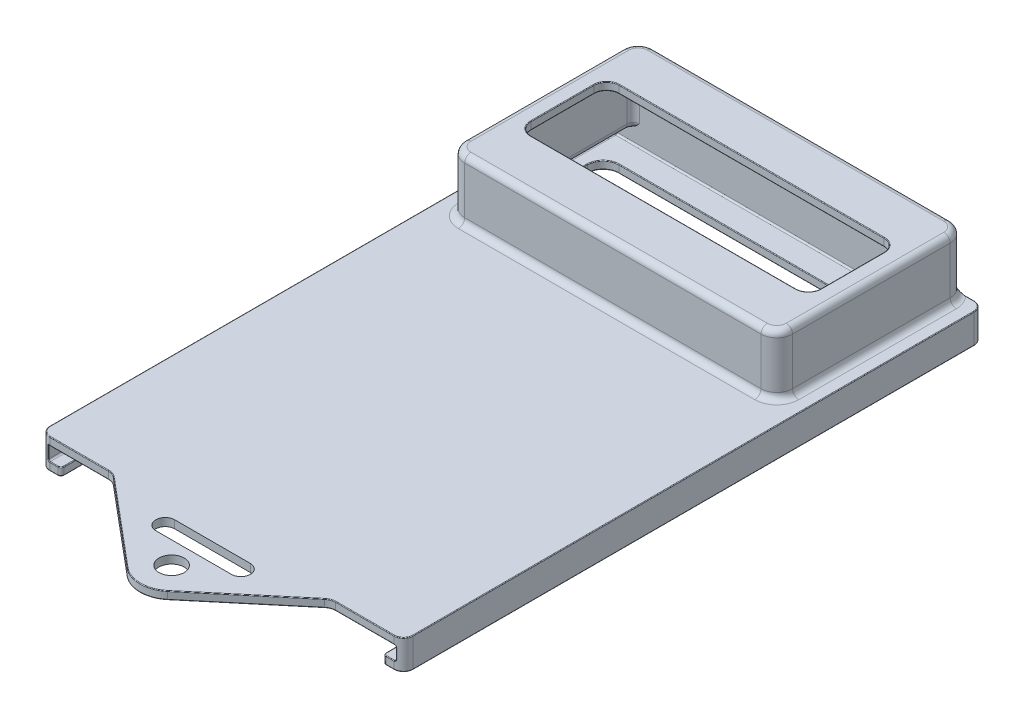
SolidWorks part; units mm, degrees
ref_plane "Спереди" through (0, 0, 0) normal (0, 0, 1) x (1, 0, 0)
ref_plane "Сверху" through (0, 0, 0) normal (0, 1, 0) x (1, 0, 0)
ref_plane "Справа" through (0, 0, 0) normal (1, 0, 0) x (0, 0, -1)
sketch "Эскиз1" plane through (0, 0, 0) normal (0, 0, 1) x (1, 0, 0)
  line L0 (-34.2552, 0) -> (0, 0) construction
  line L1 (0, 0) -> (0, 57.6) construction
  line L2 (27.55, 0) -> (-27.55, 0)
  line L3 (-27.55, 0) -> (-27.55, -2.2)
  line L4 (-27.55, -2.2) -> (-25.55, -2.2)
  line L5 (-25.55, -2.2) -> (-25.55, -3.45)
  line L6 (-25.55, -3.45) -> (-28.8, -3.45)
  line L7 (-28.8, -3.45) -> (-28.8, 1.25)
  line L8 (-28.8, 1.25) -> (28.8, 1.25)
  line L9 (28.8, -3.45) -> (28.8, 1.25)
  line L10 (25.55, -3.45) -> (28.8, -3.45)
  line L11 (25.55, -2.2) -> (25.55, -3.45)
  line L12 (27.55, -2.2) -> (25.55, -2.2)
  line L13 (27.55, 0) -> (27.55, -2.2)
  point P12 (0, 1.25)
  dimension "D1" = 55.1
  dimension "D2" = 2.2
  dimension "D3" = 1.25
  dimension "D4" = 1.25
  dimension "D5" = 57.6
  dimension "D6" = 51.1
  dimension "D7" = 1.25
extrude "Бобышка-Вытянуть1" add sketch "Эскиз1" against normal blind 92
sketch "Эскиз2" plane through (0, 0, -92) normal (0, 0, -1) x (-1, 0, 0)
  line L1 (-28.8, 1.25) -> (28.8, 1.25)
  line L2 (-28.8, 1.25) -> (-28.8, -3.45)
  line L3 (-28.8, -3.45) -> (28.8, -3.45)
  line L4 (28.8, 1.25) -> (28.8, -3.45)
extrude "Бобышка-Вытянуть2" add sketch "Эскиз2" against normal blind 2
sketch "Эскиз3" plane through (0, 1.25, 0) normal (0, 1, 0) x (1, 0, 0)
  line L0 (0, 0) -> (0, 92) construction
  line L1 (28.8, 92) -> (25.9495, 92) construction
  line L2 (-6, 2) -> (6, 2) construction
  line L3 (-6, 3) -> (6, 3)
  line L4 (-6, 1) -> (6, 1)
  line L5 (28.8, 0) -> (-28.8, 0) construction
  arc A0 (-6, 3) -> (-6, 1) centre (-6, 2) ccw
  arc A1 (6, 1) -> (6, 3) centre (6, 2) ccw
  point P7 (0, 2)
  dimension "D1" = 2
  dimension "D2" = 1
  dimension "D3" = 12
sketch "Эскиз4" plane through (0, 1.25, 0) normal (0, 1, 0) x (1, 0, 0)
  line L0 (0, 0) -> (0, 92) construction
  line L1 (28.8, 92) -> (25.9495, 92) construction
  line L3 (-26, 62) -> (26, 62)
  line L4 (-26, 62) -> (-26, 92)
  line L5 (-26, 92) -> (26, 92)
  line L6 (26, 62) -> (26, 92)
  line L7 (-26, 62) -> (26, 92) construction
  line L8 (-26, 92) -> (26, 62) construction
  point P5 (0, 77)
  dimension "D1" = 30
  dimension "D2" = 52
extrude "Бобышка-Вытянуть3" add sketch "Эскиз4" along normal blind 9.5
fillet "Скругление1" radius 2.5 4 edges at (26, 6, -92) (-26, 6, -92) (26, 6, -62) (-26, 6, -62)
fillet "Скругление2" radius 1 15 edges at (-25.2678, 1.25, -62.7322) (-26, 1.25, -77) (-25.2678, 1.25, -91.2678) (25.2678, 1.25, -91.2678) (26, 1.25, -77) (25.2678, 1.25, -62.7322) (25.2678, 10.75, -62.7322) (0, 10.75, -62) (-25.2678, 10.75, -62.7322) (-26, 10.75, -77) (-25.2678, 10.75, -91.2678) (0, 10.75, -92) (25.2678, 10.75, -91.2678) (26, 10.75, -77) (0, 1.25, -62)
sketch "Эскиз5" plane through (0, 0, 0) normal (0, -1, 0) x (1, 0, 0)
  line L9 (-26, -89.5) -> (-26, -64.5) construction
  line L10 (25.55, -90) -> (-25.55, -90) construction
  line L32 (-24.75, -64.5) -> (-24.75, -89)
  line L33 (-23.75, -90) -> (23.75, -90)
  line L34 (24.75, -89) -> (24.75, -64.5)
  line L35 (23.75, -63.5) -> (-23.75, -63.5)
  arc A24 (-23.75, -63.5) -> (-24.75, -64.5) centre (-23.75, -64.5) ccw
  arc A25 (-24.75, -89) -> (-23.75, -90) centre (-23.75, -89) ccw
  arc A26 (23.75, -90) -> (24.75, -89) centre (23.75, -89) ccw
  arc A27 (24.75, -64.5) -> (23.75, -63.5) centre (23.75, -64.5) ccw
  dimension "D4" = 1
  dimension "D1" = 26.5
  dimension "D2" = 1.25
  dimension "D3" = 49.5
extrude "Вырез-Вытянуть2" cut sketch "Эскиз5" against normal offset from surface (9.5 mm away) 1.25 up to face at (0, 10.75, -77)
fillet "Скругление3" radius 1 8 edges at (-24.4571, 9.5, -89.7071) (0, 9.5, -90) (24.4571, 9.5, -89.7071) (24.75, 9.5, -76.75) (24.4571, 9.5, -63.7929) (0, 9.5, -63.5) (-24.4571, 9.5, -63.7929) (-24.75, 9.5, -76.75)
fillet "Скругление4" radius 1 7 edges at (24.4571, 0, -89.7071) (-24.4571, 0, -89.7071) (-24.75, 0, -76.75) (-24.4571, 0, -63.7929) (0, 0, -63.5) (24.4571, 0, -63.7929) (24.75, 0, -76.75)
sketch "Эскиз7" plane through (0, 9.5, 0) normal (0, -1, 0) x (1, 0, 0)
  line L0 (0, 0) -> (0, -92) construction
  line L1 (-28.8, -92) -> (28.8, -92) construction
  line L2 (0, -101.75) -> (0, -77) construction
  line L3 (16, -84) -> (21, -84)
  line L4 (23, -82) -> (23, -72)
  line L5 (16, -70) -> (21, -70)
  line L6 (16, -84) -> (-16, -84)
  line L7 (16, -70) -> (-16, -70)
  line L8 (16, -77) -> (-16, -77) construction
  line L9 (16, -84) -> (-16, -84) construction
  line L10 (16, -70) -> (-16, -70) construction
  line L11 (0, -70) -> (0, -84) construction
  line L12 (-16, -84) -> (-21, -84)
  line L13 (-23, -82) -> (-23, -72)
  line L14 (-16, -70) -> (-21, -70)
  line L15 (0, -1.4349) -> (0, -77) construction
  line L16 (-16, -63) -> (-16, -70) construction
  line L17 (-23.5, -63) -> (23.5, -63) construction
  line L18 (-16, -84) -> (-16, -91) construction
  line L19 (23.5, -91) -> (-23.5, -91) construction
  arc A0 (21, -84) -> (23, -82) centre (21, -82) ccw
  arc A1 (21, -70) -> (23, -72) centre (21, -72) cw
  arc A2 (16, -84) -> (16, -70) centre (16, -77) ccw construction
  arc A3 (-16, -70) -> (-16, -84) centre (-16, -77) ccw construction
  arc A4 (-21, -84) -> (-23, -82) centre (-21, -82) cw
  arc A5 (-21, -70) -> (-23, -72) centre (-21, -72) ccw
  point P9 (0, -77)
  point P20 (23, -77)
  dimension "D3" = 46
  dimension "D1" = 2
  dimension "D4" = 2
  dimension "D2" = 14
  dimension "D5" = 15
  dimension "D6" = 23
extrude "Вырез-Вытянуть3" cut sketch "Эскиз7" against normal up to next
sketch "Эскиз8" plane through (0, -3.45, 0) normal (0, -1, 0) x (1, 0, 0)
  line L0 (-25.55, -90) -> (-25.55, 0) construction
  line L1 (-25.55, -86) -> (25.55, -86)
  line L2 (-25.55, -86) -> (-25.55, -90)
  line L3 (-25.55, -90) -> (25.55, -90)
  line L4 (25.55, -86) -> (25.55, -90)
  dimension "D1" = 4
extrude "Бобышка-Вытянуть4" add sketch "Эскиз8" against normal up to surface (1.25 mm away) up to face at (-26.55, -2.2, -45)
fillet "Скругление5" radius 1.5 4 edges at (-28.8, -1.1, 0) (28.8, -1.1, 0) (28.8, -1.1, -92) (-28.8, -1.1, -92)
fillet "Скругление6" radius 0.25 2 edges at (27.55, -1.1, -90) (-27.55, -1.1, -90)
sketch "Эскиз10" plane through (0, 0, 0) normal (0, -1, 0) x (1, 0, 0)
  line L0 (0, 0) -> (0, 13.6675) construction
  line L1 (6, 3) -> (-6, 3) construction
  line L2 (6, 1.5) -> (-6, 1.5)
  line L3 (6, 4.5) -> (-6, 4.5)
  line L4 (-27.3, 0) -> (27.3, 0) construction
  line L5 (-3.2139, 11.8302) -> (-17.3126, 0)
  line L6 (3.2139, 11.8302) -> (17.3126, 0)
  line L7 (-17.3126, 0) -> (-17.3126, -0.5)
  line L8 (-17.3126, -0.5) -> (17.3126, -0.5)
  line L9 (17.3126, -0.5) -> (17.3126, 0)
  circle A0 centre (0, 8) radius 2
  arc A1 (6, 1.5) -> (6, 4.5) centre (6, 3) ccw
  arc A2 (-6, 4.5) -> (-6, 1.5) centre (-6, 3) ccw
  arc A3 (3.2139, 11.8302) -> (-3.2139, 11.8302) centre (0, 8) ccw
  point P7 (0, 3)
  dimension "D1" = 4
  dimension "D6" = 10
  dimension "D2" = 3
  dimension "D3" = 12
  dimension "D4" = 3
  dimension "D5" = 5
  dimension "D7" = 40
  dimension "D8" = 0.5
extrude "Бобышка-Вытянуть6" add sketch "Эскиз10" against normal up to surface (1.25 mm away) up to face at (0, 1.25, -61.2976)
fillet "Скругление13" radius 2 2 edges at (17.3126, 0.625, 0) (-17.3126, 0.625, 0)
fillet "Скругление7" radius 0.25 9 edges at (-27.55, -2.2, -44.8855) (-27.4768, -2.2, -89.9268) (0, -2.2, -90) (27.4768, -2.2, -89.9268) (27.4768, 0, -89.9268) (27.55, -2.2, -44.8855) (27.55, 0, -44.8855) (24.9821, 0.0894, -90) (26.391, 0, -90)
fillet "Скругление8" radius 0.5 2 edges at (-25.55, -2.825, 0) (25.55, -2.825, 0)
fillet "Скругление9" radius 2.5 2 edges at (25.55, -2.825, -86) (-25.55, -2.825, -86)
fillet "Скругление10" radius 0.1 16 edges at (-24.8178, -3.45, -85.2678) (0, -3.45, -86) (24.8178, -3.45, -85.2678) (25.55, -3.45, -42) (25.6964, -3.45, -0.1464) (26.675, -3.45, 0) (28.3607, -3.45, -0.4393) (28.8, -3.45, -46) (28.3607, -3.45, -91.5607) (0, -3.45, -92) (-28.3607, -3.45, -91.5607) (-28.8, -3.45, -46) (-28.3607, -3.45, -0.4393) (-26.675, -3.45, 0) (-25.6964, -3.45, -0.1464) (-25.55, -3.45, -42)
fillet "Скругление11" radius 0.1 22 edges at (-27.55, -0.975, -0.021) (-27.4549, -2.1462, -0.008) (-26.675, -2.2, 0) (-25.6964, -2.2, -0.1464) (-25.55, -2.2, -42) (-24.8178, -2.2, -85.2678) (0, -2.2, -86) (24.8178, -2.2, -85.2678) (25.55, -2.2, -42) (25.6964, -2.2, -0.1464) (26.675, -2.2, 0) (27.4962, -2.1049, -0.0129) (27.55, -1.1, -0.021) (27.4549, -0.0538, -0.008) (22.6703, 0, 0) (-22.6703, 0, 0) (17.3565, 0, 0.1206) (9.9845, 0, 6.1491) (0, 0, 13) (-9.9845, 0, 6.1491) (-17.3565, 0, 0.1206) (-27.4254, 0, -0.0053)
extrude "Бобышка-Вытянуть5" add sketch "Эскиз3" against normal blind 4 draft 3
fillet "Скругление12" radius 0.1 8 edges at (6.9345, 0, -2) (0, 0, -2.9345) (-6.9345, 0, -2) (0, -2.75, -1.2096) (6.7904, -2.75, -2) (0, -2.75, -2.7904) (-6.7904, -2.75, -2) (0, 0, -1.0655)
fillet "Скругление14" radius 0.1 17 edges at (-25.1614, 1.383, -92) (-26.6247, 1.25, -92) (-28.3607, 1.25, -91.5607) (-28.8, 1.25, -46) (-28.3607, 1.25, -0.4393) (-22.6703, 1.25, 0) (-17.3565, 1.25, 0.1206) (-9.9845, 1.25, 6.1491) (0, 1.25, 13) (9.9845, 1.25, 6.1491) (17.3565, 1.25, 0.1206) (22.6703, 1.25, 0) (28.3607, 1.25, -0.4393) (28.8, 1.25, -46) (28.3607, 1.25, -91.5607) (26.6247, 1.25, -92) (25.1614, 1.383, -92)
fillet "Скругление15" radius 0.1 16 edges at (22.4142, 9.5, -70.5858) (23, 9.5, -77) (22.4142, 9.5, -83.4142) (0, 9.5, -84) (0, 10.75, -84) (22.4142, 10.75, -83.4142) (23, 10.75, -77) (22.4142, 10.75, -70.5858) (0, 9.5, -70) (0, 10.75, -70) (-22.4142, 9.5, -83.4142) (-23, 9.5, -77) (-22.4142, 9.5, -70.5858) (-22.4142, 10.75, -70.5858) (-23, 10.75, -77) (-22.4142, 10.75, -83.4142)
